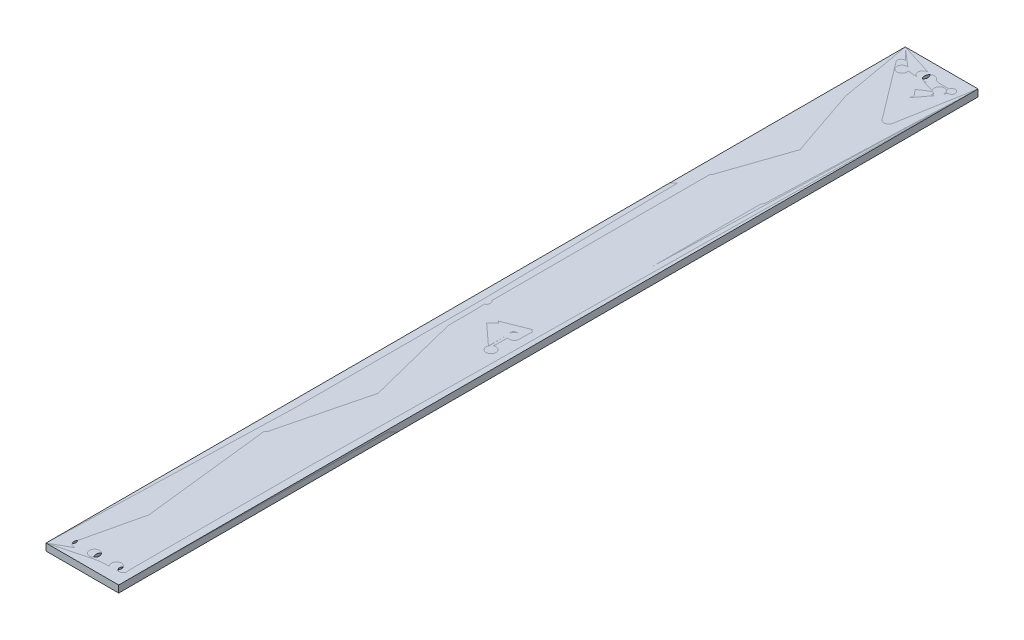
SolidWorks part; units mm, degrees
ref_plane "Front Plane" through (0, 0, 0) normal (0, 0, 1) x (1, 0, 0)
ref_plane "Top Plane" through (0, 0, 0) normal (0, 1, 0) x (1, 0, 0)
ref_plane "Right Plane" through (0, 0, 0) normal (1, 0, 0) x (0, 0, -1)
sketch "Sketch1" plane through (0, 0, 0) normal (0, 1, 0) x (1, 0, 0)
  line L1 (-16.5, -195) -> (16.5, -195)
  line L2 (-16.5, -195) -> (-16.5, 195)
  line L3 (-16.5, 195) -> (16.5, 195)
  line L4 (16.5, -195) -> (16.5, 195)
  line L5 (-16.5, -195) -> (16.5, 195) construction
  line L6 (-16.5, 195) -> (16.5, -195) construction
  point P0 (0, 0)
  dimension "D1" = 33
  dimension "D2" = 390
extrude "Boss-Extrude1" add sketch "Sketch1" along normal blind 3.175
hole_wizard "M4 Clearance Hole1" positions "Sketch4" profile "Sketch5" hole size "M4" standard "ANSI Metric" end condition through all
sketch "Sketch4" plane through (0, 3.175, 0) normal (0, 1, 0) x (1, 0, 0)
  line L4 (16.5, -195) -> (16.5, 195) construction
  line L5 (16.5, 195) -> (-16.5, 195) construction
  line L6 (-8.5, 185.5) -> (-8.5, 175.5)
  line L8 (-16.5, 195) -> (-16.5, -195) construction
  line L9 (-8.5, 162.5) -> (-8.5, -7.5)
  line L11 (-8.5, -18) -> (-8.5, -188)
  line L12 (-16.5, -195) -> (16.5, -195) construction
  line L13 (-55, 0) -> (55, 0) construction
  point P9 (1.5, 188)
  point P16 (-8.5, 185.5)
  point P17 (-8.5, 175.5)
  point P27 (-8.5, 162.5)
  point P28 (-8.5, -7.5)
  point P32 (-8.5, -18)
  point P33 (-8.5, -188)
  point P52 (1.5, -188)
  dimension "D1" = 15
  dimension "D2" = 7
  dimension "D3" = 10
  dimension "D4" = 9.5
  dimension "D5" = 8
  dimension "D6" = 170
  dimension "D7" = 13
  dimension "D8" = 10.5
  dimension "D9" = 170
  dimension "D10" = 7
sketch "Sketch5" plane through (1.5, 3.175, -188) normal (1, 0, 0) x (0, 0, 1)
  line L0 (0, 0) -> (0, 3.175)
  line L1 (0, 3.175) -> (2.25, 3.175)
  line L2 (2.25, 3.175) -> (2.25, 0)
  line L5 (2.25, 0) -> (0, 0)
  line L11 (0, -6.35) -> (0, 107.95) construction
  dimension "Thru Hole Dia." = 4.5
  dimension "Thru Hole Depth" = 3.175
hole_wizard "M4x0.7 Tapped Hole1" positions "Sketch6" profile "Sketch8" tap size "M4x0.7" standard "ANSI Metric" end condition through all
sketch "Sketch6" plane through (0, 3.175, 0) normal (0, 1, 0) x (1, 0, 0)
  line L0 (16.5, -195) -> (16.5, 195) construction
  line L1 (16.5, 195) -> (-16.5, 195) construction
  line L2 (-55, 0) -> (55, 0) construction
  line L3 (11.5, 100) -> (11.5, -100)
  line L4 (11.5, 102) -> (11.5, 112)
  point P0 (11.5, 188)
  point P9 (11.5, -188)
  point P12 (11.5, -100)
  point P20 (11.5, 0)
  point P23 (11.5, 102)
  point P24 (11.5, 112)
  point P29 (11.5, 107)
  dimension "D1" = 5
  dimension "D2" = 7
  dimension "D3" = 200
  dimension "D4" = 5
  dimension "D5" = 10
  dimension "D6" = 81
sketch "Sketch8" plane through (11.5, 3.175, -188) normal (1, 0, 0) x (0, 0, 1)
  line L0 (0, 0) -> (0, 3.175)
  line L1 (0, 3.175) -> (1.65, 3.175)
  line L2 (1.65, 3.175) -> (1.65, 0)
  line L5 (1.65, 0) -> (0, 0)
  line L11 (0, -6.35) -> (0, 107.95) construction
  dimension "Thru Tap Drill Dia." = 3.3
  dimension "Thru Tap Drill Depth" = 3.175
cosmetic thread "Hole Thread1" parameters "D2"=4
cosmetic thread "Hole Thread2" parameters "D2"=4
cosmetic thread "Hole Thread3" parameters "D2"=4
cosmetic thread "Hole Thread4" parameters "D2"=4
cosmetic thread "Hole Thread11" parameters "D2"=4
cosmetic thread "Hole Thread12" parameters "D2"=4
mirror "Mirror1" about plane through (0, 0, 0) normal (1, 0, 0) of bodies 103
cosmetic thread "Hole Thread6" parameters "D2"=4
cosmetic thread "Hole Thread7" parameters "D2"=4
cosmetic thread "Hole Thread9" parameters "D2"=4
cosmetic thread "Hole Thread10" parameters "D2"=4
cosmetic thread "Hole Thread13" parameters "D2"=4
cosmetic thread "Hole Thread14" parameters "D2"=4
